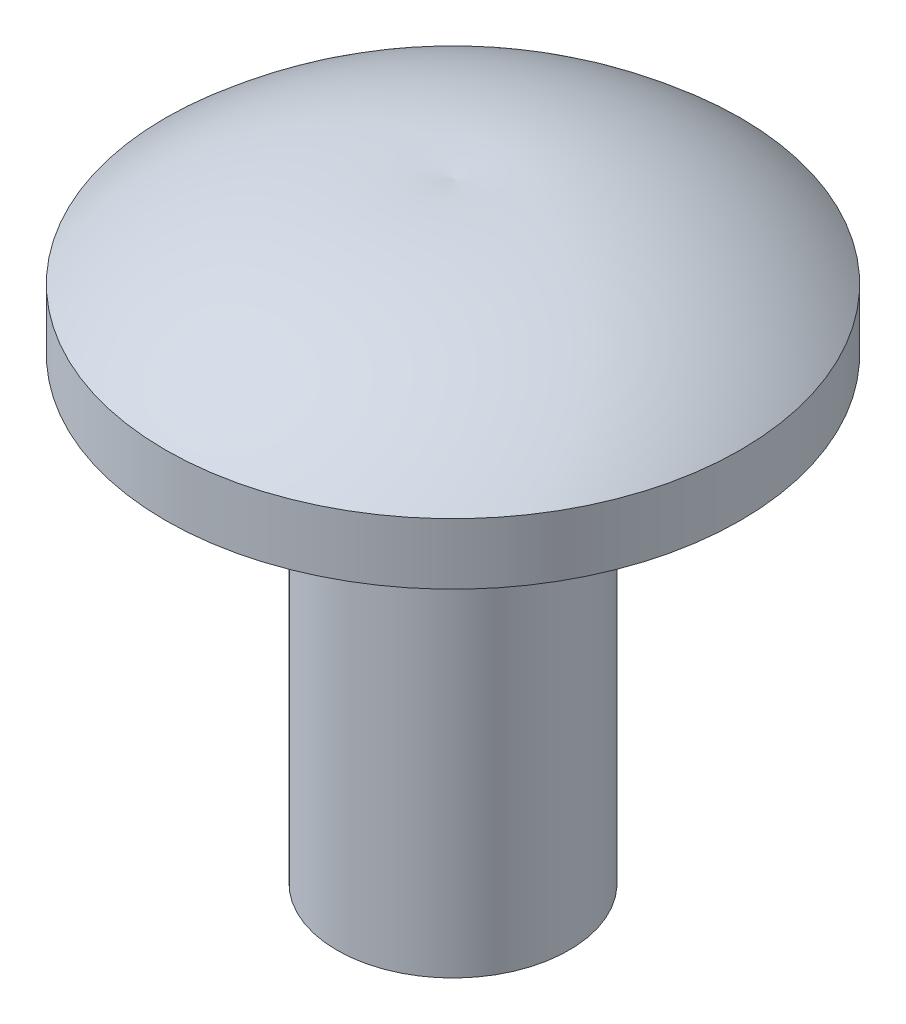
SolidWorks part; units mm, degrees
ref_plane "Front Plane" through (0, 0, 0) normal (0, 0, 1) x (1, 0, 0)
ref_plane "Top Plane" through (0, 0, 0) normal (0, 1, 0) x (1, 0, 0)
ref_plane "Right Plane" through (0, 0, 0) normal (1, 0, 0) x (0, 0, -1)
sketch "Sketch1" plane through (0, 0, 0) normal (0, 0, 1) x (1, 0, 0)
  line L0 (0, 0) -> (0, 12.7) construction
  line L1 (0, 0) -> (2.413, 0)
  line L2 (2.413, 0) -> (2.413, 9.525)
  line L3 (2.413, 9.525) -> (5.9802, 9.525)
  line L4 (5.9802, 9.525) -> (5.9802, 10.795)
  line L7 (0, 0) -> (0, 12.7)
  arc A0 (0, 12.7) -> (5.9802, 10.795) centre (0.8487, 5.0252) cw
  dimension "D3" = 7.7216
  dimension "D1" = 12.7
  dimension "D2" = 4.826
  dimension "D4" = 9.525
  dimension "D5" = 1.27
  dimension "D6" = 0.8487
revolve "Revolve1" add sketch "Sketch1" angle 360 about L7
sketch "Sketch2" plane through (0, 0, 0) normal (0, 0, 1) x (1, 0, 0)
  line L0 (0.8487, 12.7468) -> (0.8487, 11.9991)
  line L1 (0.8487, 11.9991) -> (4.1634, 11.9991)
  arc A0 (5.9802, 10.795) -> (0.8487, 12.7468) centre (0.8487, 5.0252) ccw construction
  arc A1 (4.1634, 11.9991) -> (0.8487, 12.7468) centre (0.8487, 5.0252) ccw
  point P3 (0, 0)
